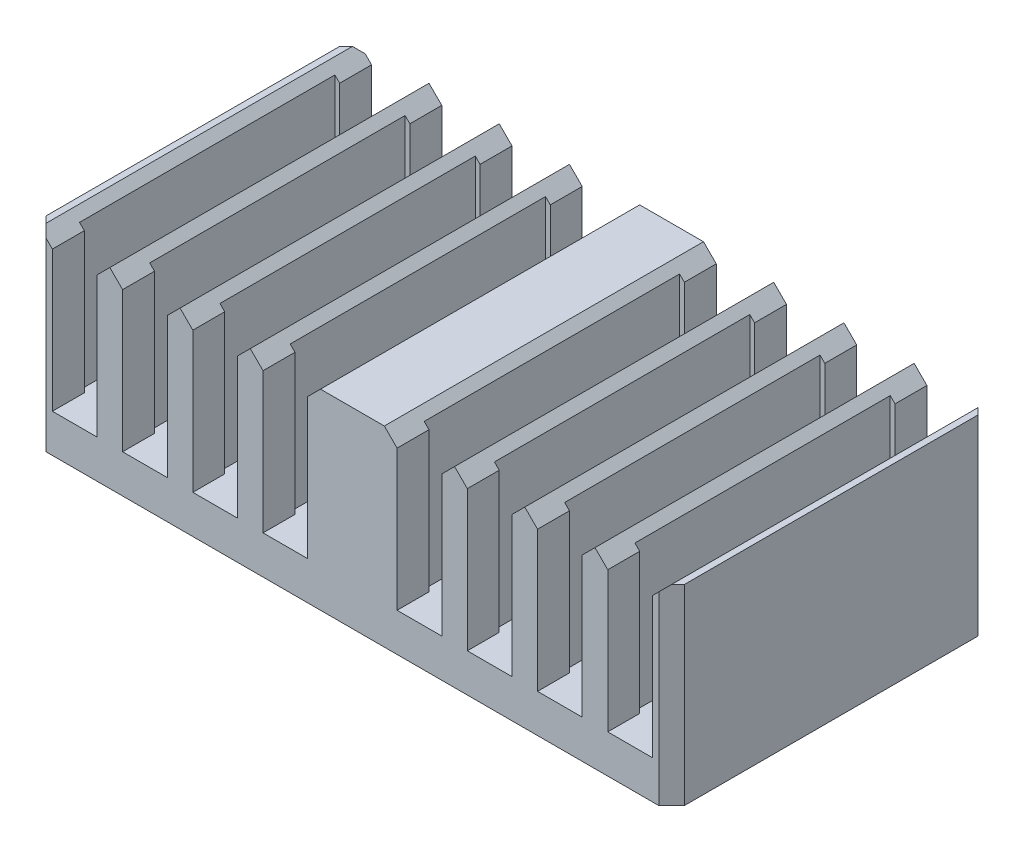
SolidWorks part; units mm, degrees
ref_plane "Front Plane" through (0, 0, 0) normal (0, 0, 1) x (1, 0, 0)
ref_plane "Top Plane" through (0, 0, 0) normal (0, 1, 0) x (1, 0, 0)
ref_plane "Right Plane" through (0, 0, 0) normal (1, 0, 0) x (0, 0, -1)
sketch "Sketch2" plane through (0, 0, 0) normal (0, 1, 0) x (1, 0, 0)
  line L1 (-25, 12.5) -> (25, 12.5)
  line L2 (-25, 12.5) -> (-25, -12.5)
  line L3 (-25, -12.5) -> (25, -12.5)
  line L4 (25, 12.5) -> (25, -12.5)
  line L5 (-25, 12.5) -> (25, -12.5) construction
  line L6 (-25, -12.5) -> (25, 12.5) construction
  point P0 (0, 0)
  dimension "D1" = 50
  dimension "D2" = 25
extrude "Boss-Extrude1" add sketch "Sketch2" along normal blind 15
sketch "Sketch4" plane through (0, 0, 12.5) normal (0, 0, 1) x (1, 0, 0)
  line L0 (-25, 15) -> (25, 15) construction
  line L1 (-23.5, 15) -> (-20, 15)
  line L2 (-23.5, 15) -> (-23.5, 3)
  line L3 (-23.5, 3) -> (-20, 3)
  line L4 (-20, 15) -> (-20, 3)
  line L5 (-23.5, 15) -> (-20, 3) construction
  line L6 (-23.5, 3) -> (-20, 15) construction
  line L7 (-25, 15) -> (-25, 0) construction
  line L39 (-21.75, 15) -> (-21.75, 3) construction
  point P4 (-21.75, 9)
  dimension "D1" = 12
  dimension "D2" = 3.5
  dimension "D3" = 1.5
extrude "Cut-Extrude1" cut sketch "Sketch4" against normal up to next contours L2 L1 L4 L3
pattern_linear "LPattern1" count 4 spacing 5.5 along (1, 0, 0) of "Cut-Extrude1"
mirror "Mirror1" about plane through (0, 0, 0) normal (1, 0, 0) of "LPattern1"
sketch "Sketch9" plane through (0, 15, 0) normal (0, 1, 0) x (1, 0, 0)
  line L0 (-23.5, 0) -> (-20, 0) construction
  line L1 (-23.5, 12.5) -> (-23.5, -12.5) construction
  line L2 (-20, 12.5) -> (-20, -12.5) construction
  line L4 (-23.875, 10) -> (-19.625, 10)
  line L5 (-23.875, 10) -> (-23.875, -10)
  line L6 (-23.875, -10) -> (-19.625, -10)
  line L7 (-19.625, 10) -> (-19.625, -10)
  line L8 (-23.875, 10) -> (-19.625, -10) construction
  line L9 (-23.875, -10) -> (-19.625, 10) construction
  point P6 (-21.75, 0)
  dimension "D1" = 4.25
  dimension "D2" = 20
extrude "Cut-Extrude3" cut sketch "Sketch9" against normal blind 12
pattern_linear "LPattern2" count 4 spacing 5.5 along (1, 0, 0) of "Cut-Extrude3"
mirror "Mirror2" about plane through (0, 0, 0) normal (1, 0, 0) of "LPattern2"
chamfer "Chamfer1" distance 1 angle 45 4 edges at (-25, 7.5, -12.5) (25, 7.5, -12.5) (25, 7.5, 12.5) (-25, 7.5, 12.5)
chamfer "Chamfer2" distance 1 angle 45 32 edges at (23.5, 15, 11.25) (20, 15, 11.25) (18, 15, 11.25) (14.5, 15, 11.25) (12.5, 15, 11.25) (9, 15, 11.25) (7, 15, 11.25) (3.5, 15, 11.25) (-3.5, 15, 11.25) (-7, 15, 11.25) (-9, 15, 11.25) (-12.5, 15, 11.25) (-14.5, 15, 11.25) (-18, 15, 11.25) (-20, 15, 11.25) (-23.5, 15, 11.25) (23.5, 15, -11.25) (20, 15, -11.25) (18, 15, -11.25) (14.5, 15, -11.25) (12.5, 15, -11.25) (9, 15, -11.25) (7, 15, -11.25) (3.5, 15, -11.25) (-3.5, 15, -11.25) (-7, 15, -11.25) (-9, 15, -11.25) (-12.5, 15, -11.25) (-14.5, 15, -11.25) (-18, 15, -11.25) (-20, 15, -11.25) (-23.5, 15, -11.25)
sketch "Sketch10" plane through (0, 0, 0) normal (0, -1, 0) x (1, 0, 0)
  line L0 (-25, 0) -> (-10, 0) construction
  line L1 (-25, -11.5) -> (-25, 11.5) construction
  line L2 (8.25, 0) -> (-8.25, 0) construction
  line L3 (0, -8.25) -> (0, 8.25) construction
  circle A0 centre (-10, 0) radius 6.1
  circle A1 centre (10, 0) radius 6.1
  dimension "D2" = 12.2
  dimension "D1" = 15
extrude "Boss-Extrude2" add sketch "Sketch10" along normal blind 3.5
fillet "Fillet2" radius 1 2 edges at (10, -3.5, 6.1) (-10, -3.5, -6.1)
